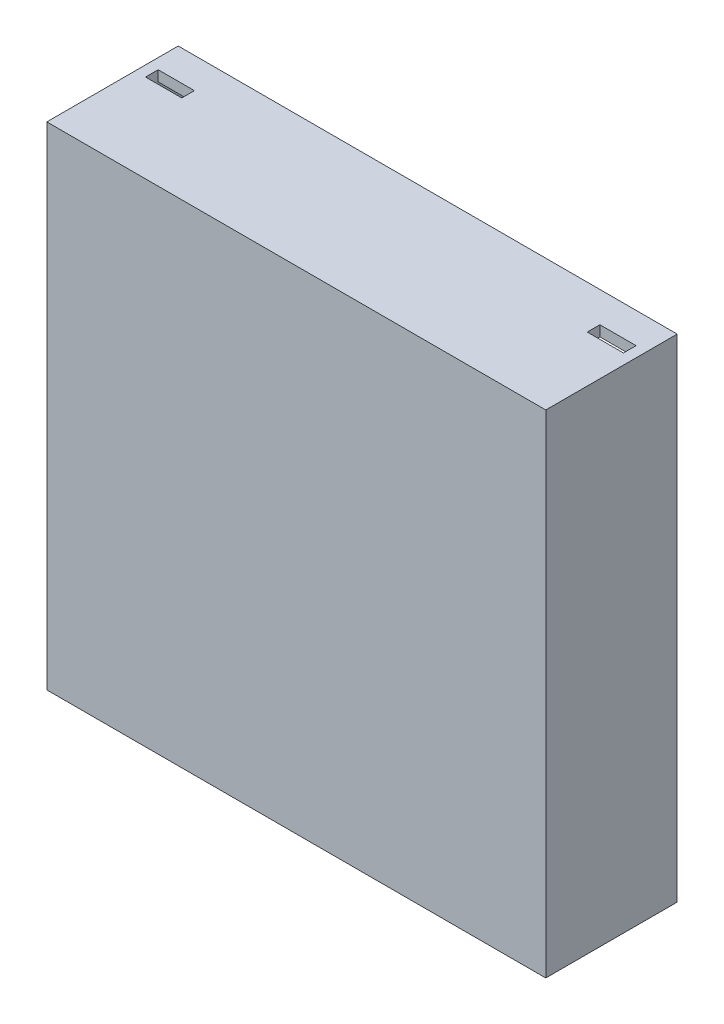
SolidWorks part; units mm, degrees
ref_plane "Front Plane" through (0, 0, 0) normal (0, 0, 1) x (1, 0, 0)
ref_plane "Top Plane" through (0, 0, 0) normal (0, 1, 0) x (1, 0, 0)
ref_plane "Right Plane" through (0, 0, 0) normal (1, 0, 0) x (0, 0, -1)
sketch "Sketch1" plane through (0, 0, 0) normal (0, 0, 1) x (1, 0, 0)
  line L0 (10.75, -9.75) -> (-121.1, -9.75) construction
  line L1 (10.75, 60.25) -> (-60.25, 60.25)
  line L2 (10.75, 60.25) -> (10.75, -9.75)
  line L3 (10.75, -9.75) -> (-60.25, -9.75)
  line L4 (-60.25, 60.25) -> (-60.25, -9.75)
  line L5 (9.25, 58.75) -> (-58.75, 58.75)
  line L6 (-58.75, 58.75) -> (-58.75, -8.25)
  line L7 (9.25, -8.25) -> (-58.75, -8.25)
  line L8 (9.25, 58.75) -> (9.25, -8.25)
  dimension "D1" = 71
  dimension "D2" = 1.5
extrude "Boss-Extrude1" add sketch "Sketch1" along normal blind 17.2
extrude "Boss-Extrude2" add sketch "Sketch1<2>" along normal blind 1.5 from surface contours L4 L3 L2 L1 starting at face at (-24.75, 25.25, 17.2)
sketch "Sketch1<2>" plane through (0, 0, 0) normal (0, 0, 1) x (1, 0, 0) same geometry as "Sketch1"
sketch "Sketch3" plane through (0, 60.25, 0) normal (0, 1, 0) x (1, 0, 0)
  line L0 (-58.75, -3) -> (-60.25, -3) construction
  line L1 (-58.75, -3) -> (-57.25, -3)
  line L2 (-58.75, -3) -> (-58.75, 0)
  line L3 (-58.75, 0) -> (-57.25, 0)
  line L4 (-57.25, -3) -> (-57.25, 0)
  line L5 (-60.25, -18.7) -> (-60.25, 0) construction
  line L6 (10.75, 0) -> (-121.1, 0) construction
  dimension "D1" = 1.5
  dimension "D2" = 3
sketch "Sketch4" plane through (-60.25, 0, 0) normal (-1, 0, 0) x (0, 0, 1)
  line L0 (3, 60.25) -> (0, 60.25) construction
  line L1 (3, 60.25) -> (-4.5, 60.25)
  line L2 (0, -9.75) -> (0, 60.25) construction
  line L3 (1.5, 61.75) -> (-4.5, 61.75)
  line L4 (0, 60.25) -> (-36.6375, 60.25) construction
  line L5 (3, 60.25) -> (0, 60.25) construction
  line L6 (3, 60.25) -> (1.5, 61.75)
  line L7 (1.5, 61.75) -> (1.5, 60.25) construction
  line L8 (-36.6375, 58.75) -> (-33.4875, 58.75) construction
  line L9 (-4.5, 61.75) -> (-6, 61.75)
  line L10 (-4.5, 61.75) -> (-4.5, 58.75)
  line L12 (-6, 61.75) -> (-6, 60.25)
  line L13 (-4.5, 58.75) -> (-6, 60.25)
  dimension "D1" = 1.5
  dimension "D2" = 3
  dimension "D3" = 45
  dimension "D4" = 6
ref_plane "Plane1" through (0, 25.25, 0) normal (0, 1, 0) x (1, 0, 0)
ref_plane "Plane2" through (-24.75, 0, 0) normal (1, 0, 0) x (0, 0, -1)
ref_plane "Plane3" through (0, 0, 20.975) normal (0, 0, 1) x (1, 0, 0)
sketch "Sketch5" plane through (0, 0, 18.7) normal (0, 0, 1) x (1, 0, 0)
  line L0 (10.75, 60.25) -> (10.75, -9.75) construction
  line L1 (-19, 25.25) -> (-25.25, 25.25) construction
  line L2 (-19, 25.25) -> (-12.75, 25.25) construction
  line L3 (-37.75, 37.75) -> (-12.75, 37.75)
  line L4 (-37.75, 37.75) -> (-37.75, 12.75) construction
  line L5 (-37.75, 12.75) -> (-12.75, 12.75) construction
  line L6 (-12.75, 37.75) -> (-12.75, 12.75) construction
  line L7 (-37.75, 37.75) -> (-12.75, 12.75) construction
  line L8 (-37.75, 12.75) -> (-12.75, 37.75) construction
  line L9 (-37.75, 25.25) -> (-60.25, 25.25) construction
  line L11 (-25.25, 37.75) -> (-25.25, 60.25) construction
  line L12 (10.75, 60.25) -> (-60.25, 60.25) construction
  circle A0 centre (-19, 25.25) radius 0.75
  point P4 (10.75, 25.25)
  point P7 (-25.25, 25.25)
  dimension "D1" = 1.5
  dimension "D3" = 25
sketch "Sketch6" plane through (0, 60.25, 0) normal (0, 1, 0) x (1, 0, 0)
  line L4 (9.25, -17.2) -> (9.25, 0) construction
  line L5 (9.25, -17.2) -> (9.25, 0) construction
  line L8 (4.1, -6.15) -> (9.4, -6.15)
  line L9 (9.4, -6.15) -> (9.4, -4.35)
  line L10 (4.1, -4.35) -> (4.1, -6.15)
  line L11 (9.4, -4.35) -> (4.1, -4.35)
  line L12 (4.1, -6.15) -> (9.25, -6.15)
  line L13 (9.25, -6.15) -> (9.25, -4.35)
  line L14 (4.1, -4.35) -> (4.1, -6.15)
  line L15 (9.25, -4.35) -> (4.1, -4.35)
  dimension "D1" = 0.15
extrude "Cut-Extrude1" cut sketch "Sketch6" against normal up to next
mirror "Mirror1" about plane through (-24.75, 0, 0) normal (1, 0, 0) of "Cut-Extrude1"
mirror "Mirror2" about plane through (0, 25.25, 0) normal (0, 1, 0) of "Mirror1", "Cut-Extrude1"
ref_axis "Axis1" through (-24.75, 25.25, -36.2629) along (0, 0, 1)
sketch "Sketch7" plane through (-60.25, 0, 0) normal (-1, 0, 0) x (0, 0, 1)
  line L8 (11.7, 12.125) -> (11.7, 33.775)
  line L9 (1.78, 12.125) -> (11.7, 12.125)
  line L10 (1.78, 33.775) -> (1.78, 12.125)
  line L11 (11.7, 33.775) -> (1.78, 33.775)
  line L12 (11.7, 12.125) -> (11.7, 33.775)
  line L13 (1.78, 12.125) -> (11.7, 12.125)
  line L14 (1.78, 33.775) -> (1.78, 12.125)
  line L15 (11.7, 33.775) -> (1.78, 33.775)
  dimension "D1" = 1
extrude "Cut-Extrude2" cut sketch "Sketch7" against normal up to next
sketch "Sketch8" plane through (0, 0, 17.2) normal (0, 0, -1) x (-1, 0, 0)
  line L0 (53.75, 13.125) -> (53.75, -0.875) construction
  line L1 (53.75, -0.875) -> (-4.25, -0.875) construction
  line L2 (53.75, 0.625) -> (53.75, -0.875)
  line L3 (53.75, -0.875) -> (52.25, -0.875)
  line L5 (53.75, -0.875) -> (52.25, -0.875)
  line L6 (53.75, -0.875) -> (53.75, 0.625)
  line L7 (53.75, 0.625) -> (52.25, 0.625)
  line L8 (52.25, -0.875) -> (52.25, 0.625)
  circle A0 centre (-1.95, 1.075) radius 0.65 construction
  circle A1 centre (-2.3, 49.625) radius 0.65 construction
  circle A2 centre (51.65, 49.525) radius 0.65 construction
  circle A3 centre (-1.95, 1.075) radius 0.65 construction
  circle A4 centre (-2.3, 49.625) radius 0.65 construction
  circle A5 centre (51.65, 49.525) radius 0.65 construction
  circle A6 centre (-2.3, 49.625) radius 2.15
  circle A7 centre (51.65, 49.525) radius 2.15
  circle A8 centre (-1.95, 1.075) radius 2.15
  circle A9 centre (51.65, 49.525) radius 0.4
  circle A10 centre (-2.3, 49.625) radius 0.4
  circle A11 centre (-1.95, 1.075) radius 0.4
  point P21 (52.5926, -0.875)
  point P29 (53.75, 0.0488)
  dimension "D3" = 1.5
  dimension "D1" = 1.5
  dimension "D2" = 0.25
extrude "Boss-Extrude6" add sketch "Sketch8" along normal up to surface (5.7 mm away) contours A7 A9 | A6 A10 | A8 A11 | L8 L3 L2 L7 region at (-53, -0.125, 17.2) region at (4.3892, 49.625, 17.2) region at (-49.5608, 49.525, 17.2) region at (4.0392, 1.075, 17.2)
equation "\"D1@Boss-Extrude1\"=14.2+3"
